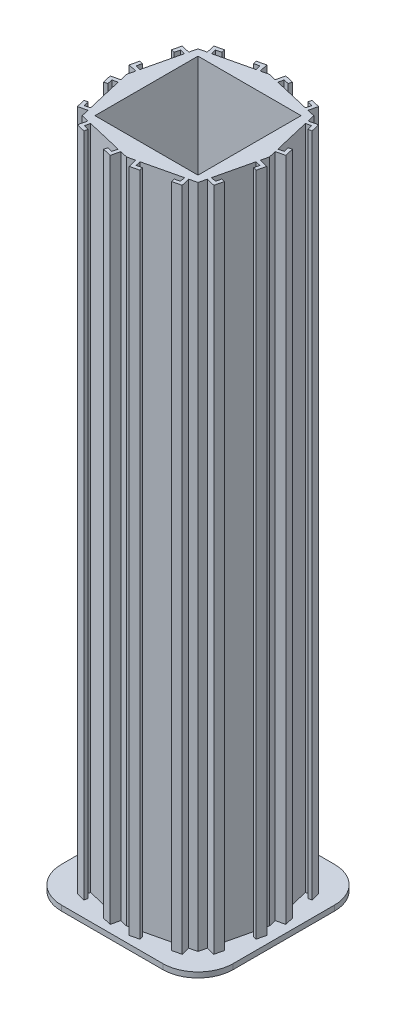
SolidWorks part; units mm, degrees
ref_plane "Front" through (0, 0, 0) normal (0, 0, 1) x (1, 0, 0)
ref_plane "Top" through (0, 0, 0) normal (0, 1, 0) x (1, 0, 0)
ref_plane "Right" through (0, 0, 0) normal (1, 0, 0) x (0, 0, -1)
sketch "Sketch1" plane through (0, 0, 0) normal (0, 1, 0) x (1, 0, 0)
  line L0 (-71.0146, 59.325) -> (-71.0146, 26.475) construction
  line L1 (-69.2146, 57.525) -> (-39.9646, 57.525)
  line L2 (-69.2146, 57.525) -> (-69.2146, 28.275)
  line L3 (-69.2146, 28.275) -> (-39.9646, 28.275)
  line L4 (-39.9646, 57.525) -> (-39.9646, 28.275)
  line L5 (-69.2146, 57.525) -> (-39.9646, 28.275) construction
  line L6 (-69.2146, 28.275) -> (-39.9646, 57.525) construction
  line L7 (-71.0146, 26.475) -> (-38.1646, 26.475) construction
  line L8 (-38.1646, 59.325) -> (-38.1646, 26.475) construction
  line L9 (-71.0146, 59.325) -> (-38.1646, 59.325) construction
  line L10 (-74.3777, 45.0286) -> (-74.8785, 42.9)
  line L11 (-38.1646, 42.9) -> (-71.0146, 42.9) construction
  line L12 (-71.0146, 59.325) -> (-54.5896, 63.1889) construction
  line L13 (-67.9126, 60.0548) -> (-57.6916, 62.4592)
  line L14 (-67.9126, 60.0548) -> (-68.2561, 61.5149)
  line L15 (-62.8021, 61.257) -> (-64.09, 66.7315) construction
  line L16 (-66.796, 61.8584) -> (-59.4952, 63.5758) construction
  line L17 (-57.6916, 62.4592) -> (-58.0351, 63.9193)
  line L18 (-68.2561, 61.5149) -> (-58.0351, 63.9193) construction
  line L19 (-68.2561, 61.5149) -> (-66.796, 61.8584)
  line L20 (-58.0351, 63.9193) -> (-59.4952, 63.5758)
  line L21 (-57.2907, 65.1217) -> (-59.7242, 64.5492)
  line L22 (-56.7182, 62.6882) -> (-57.2907, 65.1217)
  line L23 (-68.657, 58.8523) -> (-69.4585, 62.2593) construction
  line L24 (-68.886, 59.8258) -> (-69.4585, 62.2593)
  line L25 (-69.4585, 62.2593) -> (-67.0249, 62.8318)
  line L26 (-68.657, 58.8523) -> (-56.4892, 61.7147) construction
  line L27 (-56.4892, 61.7147) -> (-57.2907, 65.1217) construction
  line L28 (-56.7182, 62.6882) -> (-54.5896, 63.1889)
  line L29 (-68.886, 59.8258) -> (-71.0146, 59.325)
  line L30 (-67.0249, 62.8318) -> (-66.796, 61.8584)
  line L31 (-59.7242, 64.5492) -> (-59.4952, 63.5758)
  line L32 (-52.461, 62.6882) -> (-54.5896, 63.1889)
  line L33 (-52.461, 62.6882) -> (-51.8886, 65.1217)
  line L34 (-51.8886, 65.1217) -> (-49.455, 64.5492)
  line L35 (-49.455, 64.5492) -> (-49.684, 63.5758)
  line L36 (-51.1441, 63.9193) -> (-49.684, 63.5758)
  line L37 (-51.4876, 62.4592) -> (-51.1441, 63.9193)
  line L38 (-41.2666, 60.0548) -> (-51.4876, 62.4592)
  line L39 (-41.2666, 60.0548) -> (-40.9231, 61.5149)
  line L40 (-40.9231, 61.5149) -> (-42.3833, 61.8584)
  line L41 (-42.1543, 62.8318) -> (-42.3833, 61.8584)
  line L42 (-39.7207, 62.2593) -> (-42.1543, 62.8318)
  line L43 (-40.2932, 59.8258) -> (-38.1646, 59.325)
  line L44 (-40.2932, 59.8258) -> (-39.7207, 62.2593)
  line L45 (-40.2932, 25.9743) -> (-38.1646, 26.475)
  line L46 (-40.2932, 25.9743) -> (-39.7207, 23.5407)
  line L47 (-39.7207, 23.5407) -> (-42.1543, 22.9683)
  line L48 (-42.1543, 22.9683) -> (-42.3833, 23.9417)
  line L49 (-40.9231, 24.2852) -> (-42.3833, 23.9417)
  line L50 (-41.2666, 25.7453) -> (-40.9231, 24.2852)
  line L51 (-41.2666, 25.7453) -> (-51.4876, 23.3409)
  line L52 (-51.4876, 23.3409) -> (-51.1441, 21.8808)
  line L53 (-51.1441, 21.8808) -> (-49.684, 22.2242)
  line L54 (-49.455, 21.2508) -> (-49.684, 22.2242)
  line L55 (-51.8886, 20.6783) -> (-49.455, 21.2508)
  line L56 (-52.461, 23.1119) -> (-51.8886, 20.6783)
  line L57 (-52.461, 23.1119) -> (-54.5896, 22.6112)
  line L58 (-56.7182, 23.1119) -> (-54.5896, 22.6112)
  line L59 (-56.7182, 23.1119) -> (-57.2907, 20.6783)
  line L60 (-57.2907, 20.6783) -> (-59.7242, 21.2508)
  line L61 (-59.7242, 21.2508) -> (-59.4952, 22.2242)
  line L62 (-58.0351, 21.8808) -> (-59.4952, 22.2242)
  line L63 (-57.6916, 23.3409) -> (-58.0351, 21.8808)
  line L64 (-67.9126, 25.7453) -> (-57.6916, 23.3409)
  line L65 (-67.9126, 25.7453) -> (-68.2561, 24.2852)
  line L66 (-68.2561, 24.2852) -> (-66.796, 23.9417)
  line L67 (-67.0249, 22.9683) -> (-66.796, 23.9417)
  line L68 (-69.4585, 23.5407) -> (-67.0249, 22.9683)
  line L69 (-68.886, 25.9743) -> (-69.4585, 23.5407)
  line L70 (-68.886, 25.9743) -> (-71.0146, 26.475)
  line L71 (-71.0146, 59.325) -> (-71.0146, 26.475) construction
  line L72 (-34.8015, 40.7715) -> (-34.3008, 42.9)
  line L73 (-34.8015, 40.7715) -> (-32.3679, 40.199)
  line L74 (-32.3679, 40.199) -> (-32.9404, 37.7654)
  line L75 (-32.9404, 37.7654) -> (-33.9138, 37.9944)
  line L76 (-33.5703, 39.4545) -> (-33.9138, 37.9944)
  line L77 (-35.0305, 39.798) -> (-33.5703, 39.4545)
  line L78 (-37.4349, 29.577) -> (-35.0305, 39.798)
  line L79 (-37.4349, 29.577) -> (-35.9747, 29.2335)
  line L80 (-35.9747, 29.2335) -> (-35.6313, 30.6937)
  line L81 (-34.6578, 30.4647) -> (-35.6313, 30.6937)
  line L82 (-35.2303, 28.0311) -> (-34.6578, 30.4647)
  line L83 (-37.6639, 28.6036) -> (-35.2303, 28.0311)
  line L84 (-37.6639, 28.6036) -> (-38.1646, 26.475)
  line L85 (-37.6639, 57.1965) -> (-38.1646, 59.325)
  line L86 (-37.6639, 57.1965) -> (-35.2303, 57.7689)
  line L87 (-35.2303, 57.7689) -> (-34.6578, 55.3354)
  line L88 (-34.6578, 55.3354) -> (-35.6313, 55.1064)
  line L89 (-35.9747, 56.5665) -> (-35.6313, 55.1064)
  line L90 (-37.4349, 56.223) -> (-35.9747, 56.5665)
  line L91 (-37.4349, 56.223) -> (-35.0305, 46.002)
  line L92 (-35.0305, 46.002) -> (-33.5703, 46.3455)
  line L93 (-33.5703, 46.3455) -> (-33.9138, 47.8057)
  line L94 (-32.9404, 48.0347) -> (-33.9138, 47.8057)
  line L95 (-32.3679, 45.6011) -> (-32.9404, 48.0347)
  line L96 (-34.8015, 45.0286) -> (-32.3679, 45.6011)
  line L97 (-34.8015, 45.0286) -> (-34.3008, 42.9)
  line L98 (-54.5896, 59.325) -> (-54.5896, 26.475) construction
  line L99 (-74.3777, 45.0286) -> (-76.8113, 45.6011)
  line L100 (-76.8113, 45.6011) -> (-76.2388, 48.0347)
  line L101 (-76.2388, 48.0347) -> (-75.2654, 47.8057)
  line L102 (-75.6089, 46.3455) -> (-75.2654, 47.8057)
  line L103 (-74.1487, 46.002) -> (-75.6089, 46.3455)
  line L104 (-71.7443, 56.223) -> (-74.1487, 46.002)
  line L105 (-71.7443, 56.223) -> (-73.2045, 56.5665)
  line L106 (-73.2045, 56.5665) -> (-73.548, 55.1064)
  line L107 (-74.5214, 55.3354) -> (-73.548, 55.1064)
  line L108 (-73.9489, 57.7689) -> (-74.5214, 55.3354)
  line L109 (-71.5153, 57.1965) -> (-73.9489, 57.7689)
  line L110 (-71.5153, 57.1965) -> (-71.0146, 59.325)
  line L111 (-71.5153, 28.6036) -> (-71.0146, 26.475)
  line L112 (-71.5153, 28.6036) -> (-73.9489, 28.0311)
  line L113 (-73.9489, 28.0311) -> (-74.5214, 30.4647)
  line L114 (-74.5214, 30.4647) -> (-73.548, 30.6937)
  line L115 (-73.2045, 29.2335) -> (-73.548, 30.6937)
  line L116 (-71.7443, 29.577) -> (-73.2045, 29.2335)
  line L117 (-71.7443, 29.577) -> (-74.1487, 39.798)
  line L118 (-74.1487, 39.798) -> (-75.6089, 39.4545)
  line L119 (-75.6089, 39.4545) -> (-75.2654, 37.9944)
  line L120 (-76.2388, 37.7654) -> (-75.2654, 37.9944)
  line L121 (-76.8113, 40.199) -> (-76.2388, 37.7654)
  line L122 (-74.3777, 40.7715) -> (-76.8113, 40.199)
  line L123 (-74.3777, 40.7715) -> (-74.8785, 42.9)
  point P0 (-54.5896, 42.9)
  point P14 (-62.8021, 61.257)
  dimension "D1" = 29.25
  dimension "D3" = 10.5
  dimension "D4" = 1.5
  dimension "D5" = 7.5
  dimension "D2" = 1.8
  dimension "D6" = 1
extrude "Boss-Extrude1" add sketch "Sketch1" along normal blind 189
sketch "Sketch2" plane through (0, 0, 0) normal (0, -1, 0) x (1, 0, 0)
  line L0 (-69.2146, -28.275) -> (-69.2146, -57.525) construction
  line L1 (-69.2146, -57.525) -> (-69.2146, -28.275) construction
  line L2 (-69.2146, -57.525) -> (-39.9646, -57.525) construction
  line L3 (-39.9646, -57.525) -> (-39.9646, -28.275) construction
  line L4 (-39.9646, -28.275) -> (-69.2146, -28.275) construction
  line L5 (-68.9646, -28.525) -> (-68.9646, -57.275)
  line L6 (-68.9646, -57.275) -> (-40.2146, -57.275)
  line L7 (-40.2146, -57.275) -> (-40.2146, -28.525)
  line L8 (-40.2146, -28.525) -> (-68.9646, -28.525)
  line L9 (-67.7646, -29.725) -> (-67.7646, -56.075)
  line L10 (-67.7646, -56.075) -> (-41.4146, -56.075)
  line L11 (-41.4146, -56.075) -> (-41.4146, -29.725)
  line L12 (-41.4146, -29.725) -> (-67.7646, -29.725)
  line L13 (-54.5896, -29.725) -> (-54.5896, -56.075) construction
  line L14 (-67.7646, -42.9) -> (-41.4146, -42.9) construction
  dimension "D1" = 0.25
  dimension "D2" = 1.2
extrude "Boss-Extrude2" add sketch "Sketch2" against normal blind 10 separate body
sketch "Sketch3" plane through (0, 0, 0) normal (0, -1, 0) x (1, 0, 0)
  line L10 (-78.9646, -67.275) -> (-30.2146, -67.275)
  line L11 (-30.2146, -67.275) -> (-30.2146, -18.525)
  line L12 (-30.2146, -18.525) -> (-78.9646, -18.525)
  line L13 (-78.9646, -18.525) -> (-78.9646, -67.275)
  line L14 (-68.9646, -67.275) -> (-40.2146, -67.275)
  line L15 (-30.2146, -57.275) -> (-30.2146, -28.525)
  line L16 (-40.2146, -18.525) -> (-68.9646, -18.525)
  line L17 (-78.9646, -28.525) -> (-78.9646, -57.275)
  arc A0 (-40.2146, -18.525) -> (-30.2146, -28.525) centre (-40.2146, -28.525) cw
  arc A1 (-30.2146, -57.275) -> (-40.2146, -67.275) centre (-40.2146, -57.275) cw
  arc A2 (-68.9646, -67.275) -> (-78.9646, -57.275) centre (-68.9646, -57.275) cw
  arc A3 (-68.9646, -18.525) -> (-78.9646, -28.525) centre (-68.9646, -28.525) ccw
  circle A4 centre (-54.6645, -42.7165) radius 1.5
  dimension "D2" = 10
  dimension "D1" = 10
extrude "Boss-Extrude3" add sketch "Sketch3" along normal blind 1.5
sketch "Sketch4" plane through (0, 0, 0) normal (0, 1, 0) x (1, 0, 0)
  line L0 (-54.6645, 42.7165) -> (-56.1895, 45.3578) construction
  line L1 (-51.6145, 42.7165) -> (-53.1395, 45.3578)
  line L2 (-53.1395, 45.3578) -> (-56.1895, 45.3578)
  line L3 (-56.1895, 45.3578) -> (-57.7145, 42.7165)
  line L4 (-57.7145, 42.7165) -> (-56.1895, 40.0751)
  line L5 (-56.1895, 40.0751) -> (-53.1395, 40.0751)
  line L6 (-53.1395, 40.0751) -> (-51.6145, 42.7165)
  line L7 (-54.6645, 67.0219) -> (-54.5896, 18.525) construction
  line L8 (-40.2146, 18.525) -> (-68.9646, 18.525) construction
  circle A0 centre (-54.6645, 42.7165) radius 5
  circle A1 centre (-54.6645, 42.7165) radius 2.6414 construction
  dimension "D1" = 3.05
  dimension "D2" = 48.4969
extrude "Boss-Extrude4" add sketch "Sketch4" along normal blind 2.5
fillet "Fillet1" radius 2.5 1 edges at (-54.6645, 0, -37.7165) type face fillet first side face at (-54.6645, 2.5, -37.7165) second side face at (-54.5896, 0, -42.9)
